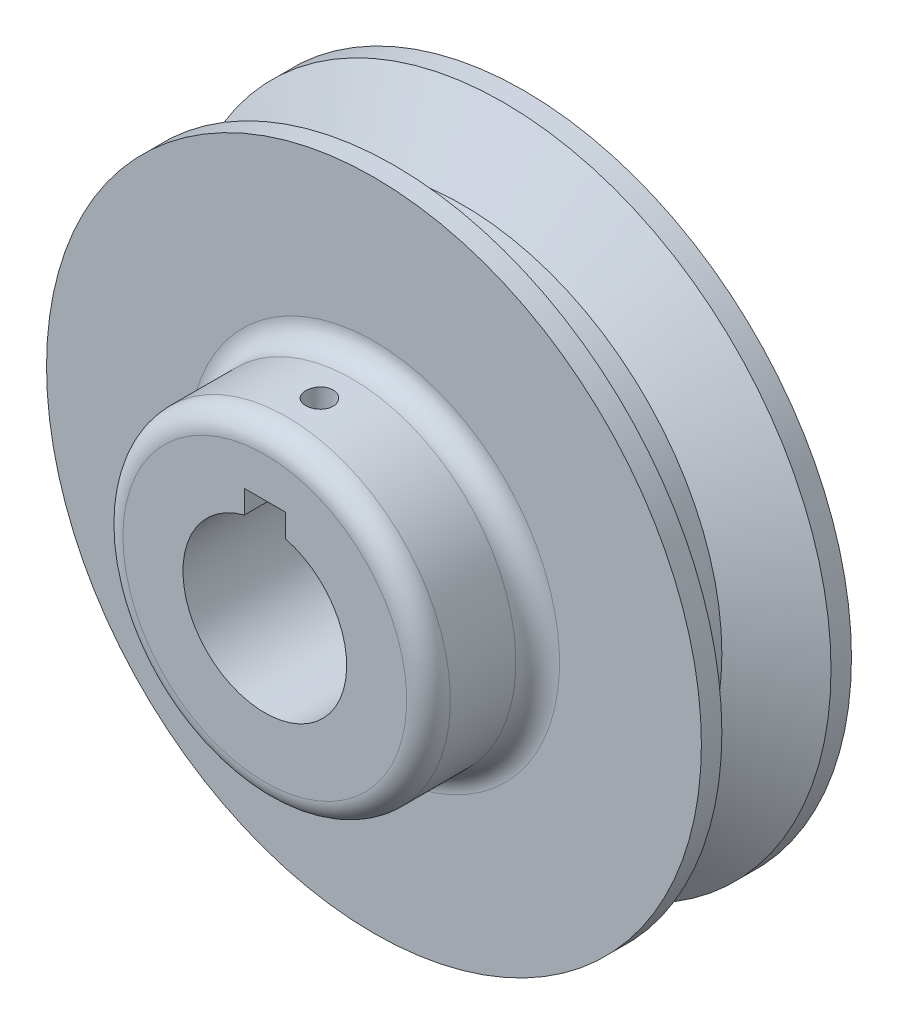
SolidWorks part; units mm, degrees
material "6061 Alloy"
ref_plane "Front Plane" through (0, 0, 0) normal (0, 0, 1) x (1, 0, 0)
ref_plane "Top Plane" through (0, 0, 0) normal (0, 1, 0) x (1, 0, 0)
ref_plane "Right Plane" through (0, 0, 0) normal (1, 0, 0) x (0, 0, -1)
sketch "Sketch3" plane through (0, 0, 0) normal (1, 0, 0) x (0, 0, -1)
  line L0 (0, 9.525) -> (30.1625, 9.525)
  line L1 (30.1625, 9.525) -> (30.1625, 38.1)
  line L2 (30.1625, 38.1) -> (27.7812, 38.1)
  line L3 (23.0187, 30.1625) -> (19.8437, 30.1625)
  line L4 (12.7, 38.1) -> (15.0812, 38.1)
  line L5 (12.7, 38.1) -> (12.7, 19.05)
  line L6 (12.7, 19.05) -> (0, 19.05)
  line L7 (0, 19.05) -> (0, 9.525)
  line L8 (15.0812, 38.1) -> (19.8437, 30.1625)
  line L9 (27.7812, 38.1) -> (23.0187, 30.1625)
  line L10 (0, 0) -> (115.3497, 0) construction
  dimension "D1" = 30.1625
  dimension "D2" = 17.4625
  dimension "D3" = 7.9375
  dimension "D4" = 3.175
  dimension "D5" = 4.7625
  dimension "D6" = 12.7
  dimension "D7" = 38.1
  dimension "D8" = 9.525
  dimension "D9" = 19.05
revolve "Revolve2" add sketch "Sketch3" angle 360 about L10
sketch "Sketch4" plane through (0, 0, 0) normal (0, 0, 1) x (1, 0, 0)
  line L1 (2.3813, 7.1437) -> (-2.3812, 7.1437)
  line L2 (2.3813, 7.1437) -> (2.3813, 11.9062)
  line L3 (2.3813, 11.9062) -> (-2.3813, 11.9062)
  line L4 (-2.3812, 7.1437) -> (-2.3813, 11.9062)
  dimension "D1" = 4.7625
  dimension "D2" = 4.7625
  dimension "D3" = 7.1437
  dimension "D4" = 2.3813
extrude "Cut-Extrude2" cut sketch "Sketch4" against normal through all
sketch "Sketch5" plane through (0, 0, 0) normal (0, 1, 0) x (1, 0, 0)
  line L0 (-19.05, 0) -> (19.05, 0) construction
  line L1 (-19.05, 12.7) -> (-19.05, 0) construction
  circle A0 centre (0, 6.35) radius 1.5875
  dimension "D3" = 3.175
  dimension "D1" = 6.35
  dimension "D2" = 19.05
extrude "Cut-Extrude3" cut sketch "Sketch5" along normal through all
fillet "Fillet1" radius 2.54 2 edges at (19.05, 0, -12.7) (19.05, 0, 0)
